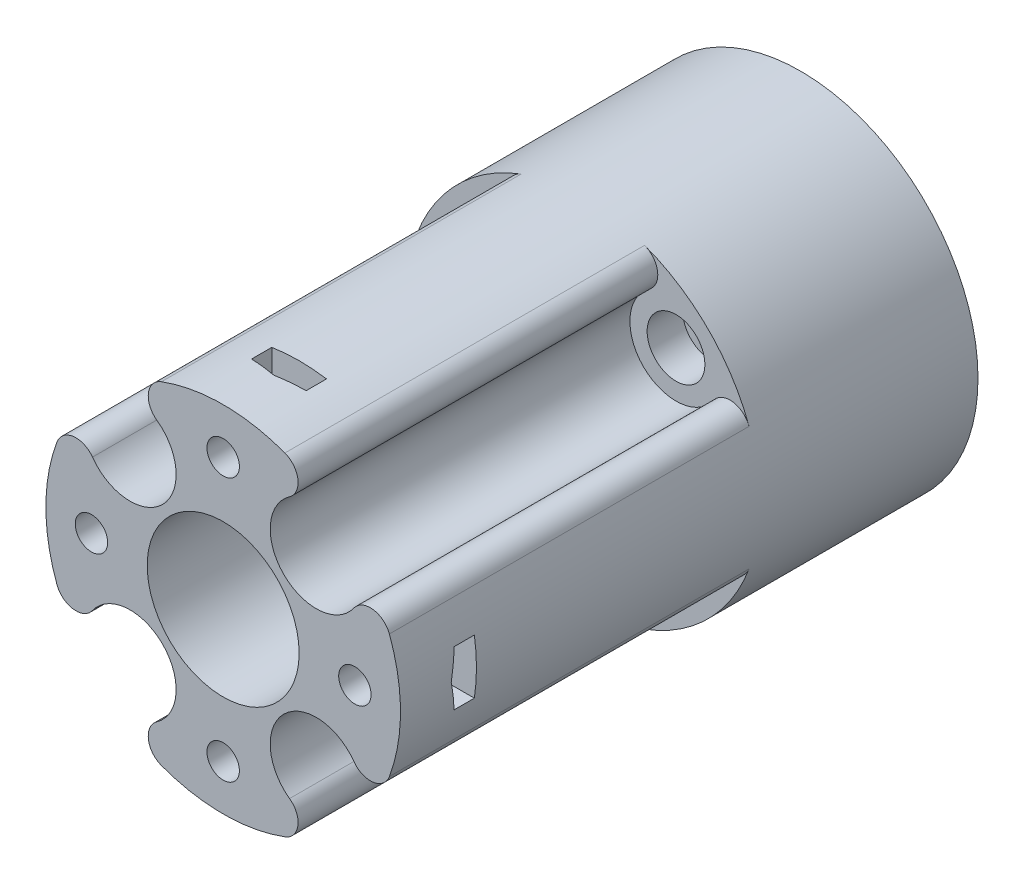
SolidWorks part; units mm, degrees
ref_plane "Front Plane" through (0, 0, 0) normal (1, 0, 0) x (0, 1, 0)
ref_plane "Top Plane" through (0, 0, 0) normal (0, 0, 1) x (0, 1, 0)
ref_plane "Right Plane" through (0, 0, 0) normal (0, 1, 0) x (-1, 0, 0)
sketch "Sketch1" plane through (0, 0, 0) normal (0, 0, 1) x (0, 1, 0)
  line L0 (0, 0) -> (9.1924, 9.1924) construction
  circle A0 centre (0, 0) radius 17.5
  circle A1 centre (0, 0) radius 13 construction
  circle A2 centre (9.1924, 9.1924) radius 1.6
  circle A3 centre (9.1924, 9.1924) radius 2.85
  circle A4 centre (9.1924, -9.1924) radius 2.85
  circle A5 centre (9.1924, -9.1924) radius 1.6
  circle A6 centre (-9.1924, -9.1924) radius 2.85
  circle A7 centre (-9.1924, -9.1924) radius 1.6
  circle A8 centre (-9.1924, 9.1924) radius 2.85
  circle A9 centre (-9.1924, 9.1924) radius 1.6
  point P19 (0, 0)
  dimension "D1" = 35
  dimension "D2" = 26
  dimension "D3" = 3.2
  dimension "D4" = 5.7
  dimension "D5" = 4
extrude "Boss-Extrude1" add sketch "Sketch1" along normal blind 57 contours A0 A8 A6 A4 A3 region at (0, 0, 0)
extrude "Boss-Extrude2" add sketch "Sketch1<3>" along normal blind 18 contours A6 A7 | A8 A9 | A4 A5 | A3 A2 region at (-9.1924, 6.423, 0) region at (9.1924, 6.423, 0) region at (9.1924, -11.9618, 0) region at (-9.1924, -11.9618, 0)
sketch "Sketch1<3>" plane through (0, 0, 0) normal (0, 0, 1) x (0, 1, 0) same geometry as "Sketch1"
sketch "Sketch2" plane through (0, 0, 57) normal (0, 0, 1) x (1, 0, 0)
  circle A0 centre (-9.1924, 9.1924) radius 4.55
  circle A1 centre (9.1924, 9.1924) radius 4.55
  circle A2 centre (9.1924, -9.1924) radius 4.55
  circle A3 centre (-9.1924, -9.1924) radius 4.55
  dimension "D1" = 9.1
  dimension "D2" = 2
  dimension "D3" = 2
extrude "Cut-Extrude1" cut sketch "Sketch2" against normal offset from surface (35.5 mm away) 3.5 up to face at (-7.5924, -9.1924, 18)
fillet "Fillet1" radius 2 8 edges at (12.9138, 11.8103, 39.25) (-12.9138, 11.8103, 39.25) (-11.8103, 12.9138, 39.25) (11.8103, 12.9138, 39.25) (12.9138, -11.8103, 39.25) (11.8103, -12.9138, 39.25) (-11.8103, -12.9138, 39.25) (-12.9138, -11.8103, 39.25)
sketch "Sketch3" plane through (0, 0, 57) normal (0, 0, 1) x (1, 0, 0)
  line L0 (-2.6998, 15.6993) -> (-2.6998, 17.2905)
  line L2 (-2.6998, 15.6993) -> (-2.6998, 10.3002)
  line L3 (-2.6998, 10.3002) -> (2.7002, 10.3002)
  line L4 (2.7002, 15.7002) -> (2.7002, 10.3002)
  line L5 (-2.6998, 15.6993) -> (2.7002, 10.3002) construction
  line L6 (-2.6998, 10.3002) -> (2.7002, 15.7002) construction
  line L7 (2.7002, 15.7002) -> (2.7002, 17.2904)
  line L8 (15.7002, -2.7002) -> (10.3002, -2.7002)
  line L9 (10.3002, 2.6998) -> (10.3002, -2.7002)
  line L10 (15.6993, 2.6998) -> (10.3002, 2.6998)
  line L11 (15.6993, 2.6998) -> (17.2905, 2.6998)
  line L12 (15.7002, -2.7002) -> (17.2904, -2.7002)
  line L13 (-2.7002, -15.7002) -> (-2.7002, -10.3002)
  line L14 (2.6998, -10.3002) -> (-2.7002, -10.3002)
  line L15 (2.6998, -15.6993) -> (2.6998, -10.3002)
  line L16 (2.6998, -15.6993) -> (2.6998, -17.2905)
  line L17 (-2.7002, -15.7002) -> (-2.7002, -17.2904)
  line L18 (-15.7002, 2.7002) -> (-10.3002, 2.7002)
  line L19 (-10.3002, -2.6998) -> (-10.3002, 2.7002)
  line L20 (-15.6993, -2.6998) -> (-10.3002, -2.6998)
  line L21 (-15.6993, -2.6998) -> (-17.2905, -2.6998)
  line L22 (-15.7002, 2.7002) -> (-17.2904, 2.7002)
  circle A0 centre (0, 0) radius 13 construction
  circle A2 centre (0, 13) radius 1.6
  circle A3 centre (0, 0) radius 17.5 construction
  arc A4 (-2.6998, 17.2905) -> (2.7002, 17.2904) centre (0, 0) cw
  arc A5 (17.2905, 2.6998) -> (17.2904, -2.7002) centre (0, 0) cw
  circle A6 centre (13, 0) radius 1.6
  arc A7 (2.6998, -17.2905) -> (-2.7002, -17.2904) centre (0, 0) cw
  circle A8 centre (0, -13) radius 1.6
  arc A9 (-17.2905, -2.6998) -> (-17.2904, 2.7002) centre (0, 0) cw
  circle A10 centre (-13, 0) radius 1.6
  point P41 (0, 0)
  dimension "D1" = 26
  dimension "D2" = 3.2
  dimension "D3" = 5.4
  dimension "D4" = 5.4
  dimension "D5" = 4
extrude "Cut-Extrude2" cut sketch "Sketch3" against normal blind 2.5 from offset 5 offset against normal yes
extrude "Cut-Extrude3" cut sketch "Sketch3<2>" against normal blind 10 contours A10 | A2 | A6 | A8 region at (0, 13, 57) region at (13, 0, 57) region at (0, -13, 57) region at (-13, 0, 57)
sketch "Sketch3<2>" plane through (0, 0, 57) normal (0, 0, 1) x (1, 0, 0) same geometry as "Sketch3"
chamfer "Chamfer1" distance 2.75 distance2 0.5 8 edges at (-13.7954, -2.6998, 52) (-2.6998, 13.7954, 52) (2.7002, 13.7953, 52) (13.7954, 2.6998, 52) (13.7953, -2.7002, 52) (2.6998, -13.7954, 52) (-2.7002, -13.7953, 52) (-13.7953, 2.7002, 52) first distance on face at (-14.6, 0, 52) first distance on face at (-1.6, 13, 52) first distance on face at (11.4, 0, 52) first distance on face at (-1.6, -13, 52)
sketch "Sketch4" plane through (0, 0, 57) normal (0, 0, 1) x (1, 0, 0)
  circle A0 centre (0, 0) radius 7.5
  dimension "D1" = 15
extrude "Cut-Extrude4" cut sketch "Sketch4" against normal through all contours A0
sketch "Sketch5" plane through (0, 0, 0) normal (0, 0, -1) x (1, 0, 0)
  circle A0 centre (0, 13) radius 2
  circle A1 centre (0, 0) radius 13 construction
  circle A2 centre (13, 0) radius 2
  circle A3 centre (0, 0) radius 13 construction
  circle A4 centre (0, -13) radius 2
  circle A5 centre (0, 0) radius 13 construction
  circle A6 centre (-13, 0) radius 2
  circle A7 centre (0, 0) radius 13 construction
  point P18 (0, 0)
  dimension "D1" = 4
  dimension "D2" = 4
extrude "Cut-Extrude5" cut sketch "Sketch5" against normal blind 10
